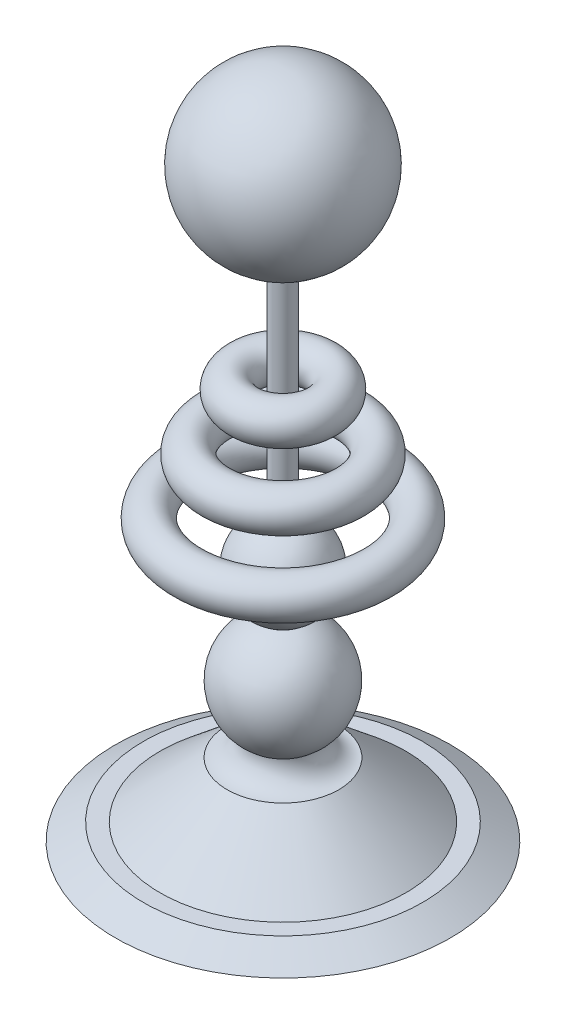
SolidWorks part; units mm, degrees
ref_plane "Front" through (0, 0, 0) normal (0, 0, 1) x (1, 0, 0)
ref_plane "Top" through (0, 0, 0) normal (0, 1, 0) x (1, 0, 0)
ref_plane "Right" through (0, 0, 0) normal (1, 0, 0) x (0, 0, -1)
sketch "草图1" plane through (0, 0, 0) normal (0, 0, 1) x (1, 0, 0)
  line L0 (0, 0) -> (30, 0)
  line L1 (30, 0) -> (25, 3)
  line L2 (25, 3) -> (22, 3)
  line L3 (22, 3) -> (10, 13)
  line L4 (10, 13) -> (6, 13)
  line L5 (6, 13) -> (6, 17)
  line L6 (0, 0) -> (0, 120) construction
  line L7 (2, 90.1339) -> (2, 50.2899)
  arc A0 (6, 17) -> (2, 34.798) centre (0, 25) ccw
  arc A1 (2, 34.798) -> (2, 50.2899) centre (0, 42.5439) ccw
  arc A2 (2, 90.1339) -> (0, 120) centre (0, 105) ccw
  circle A3 centre (7, 70.1339) radius 3.5
  circle A4 centre (12, 60.1339) radius 3.5
  circle A5 centre (17, 50.1339) radius 3.5
  dimension "D9" = 10
  dimension "D10" = 8
  dimension "D13" = 15
  dimension "D14" = 7
  dimension "D15" = 7
  dimension "D16" = 7
  dimension "D1" = 30
  dimension "D2" = 3
  dimension "D3" = 5
  dimension "D4" = 3
  dimension "D5" = 10
  dimension "D6" = 10
  dimension "D7" = 4
  dimension "D8" = 4
  dimension "D11" = 2
  dimension "D12" = 120
  dimension "D17" = 20
  dimension "D18" = 30
  dimension "D19" = 40
  dimension "D20" = 5
  dimension "D21" = 5
  dimension "D22" = 5
revolve "旋转1" add sketch "草图1" angle 360 about L6 region at (1.2369, 60, 0)
fillet "圆角3" radius 4 1 edges at (0, 13, -6)
